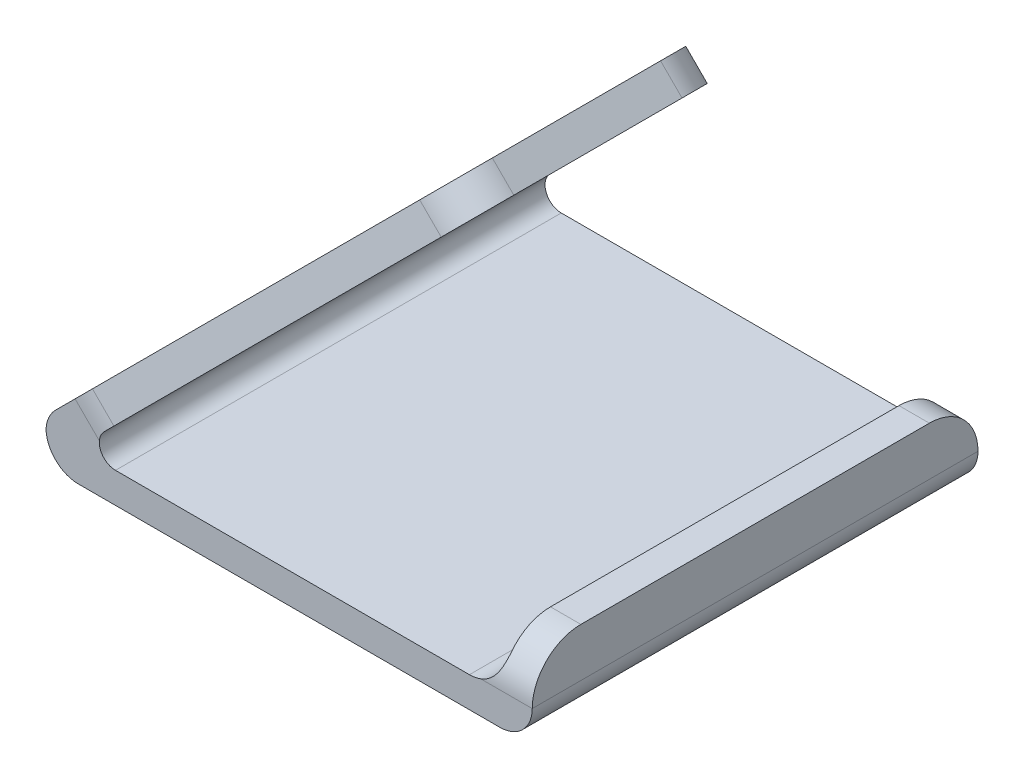
SolidWorks part; units mm, degrees
ref_plane "Front Plane" through (0, 0, 0) normal (0, 0, 1) x (1, 0, 0)
ref_plane "Top Plane" through (0, 0, 0) normal (0, 1, 0) x (1, 0, 0)
ref_plane "Right Plane" through (0, 0, 0) normal (1, 0, 0) x (0, 0, -1)
sketch "Sketch1" plane through (0, 0, 0) normal (0, 0, 1) x (1, 0, 0)
  line L0 (-76.2, 6.7352) -> (-27.9984, 54.9368)
  line L1 (0, 0) -> (-76.2, 0)
  line L2 (0, 0) -> (0, 6.6302)
  line L3 (-4.7625, 4.7625) -> (-71.4375, 4.7625)
  line L4 (-76.2, 0) -> (-76.2, 6.7352)
  line L5 (-27.9984, 54.9368) -> (-24.6308, 51.5692)
  line L6 (-24.6308, 51.5692) -> (-71.4375, 4.7625)
  line L7 (-4.7625, 4.7625) -> (-4.7625, 12.7)
  line L8 (-4.7625, 12.7) -> (0, 12.7)
  line L9 (0, 12.7) -> (0, 6.6302)
  line L10 (-24.6308, 51.5692) -> (-4.7625, 4.7625) construction
  dimension "D1" = 4.7625
  dimension "D2" = 4.7625
  dimension "D3" = 4.7625
  dimension "D4" = 45
  dimension "D5" = 76.2
  dimension "D6" = 4.7625
  dimension "D7" = 23
  dimension "D8" = 12.7
extrude "Boss-Extrude1" add sketch "Sketch1" along normal blind 69.85
fillet "Fillet1" radius 5.08 4 edges at (-76.2, 0, 34.925) (-76.2, 6.7352, 34.925) (0, 0, 34.925) (-4.7625, 4.7625, 34.925)
fillet "Fillet3" radius 2.54 1 edges at (-71.4375, 4.7625, 34.925)
sketch "Sketch2" plane through (-41.4676, 41.4676, 0) normal (-0.7071, 0.7071, 0) x (0, 0, 1)
  line L0 (15.875, 19.0484) -> (0, -41.0142)
  line L1 (69.85, 19.0484) -> (0, 19.0484) construction
  line L2 (69.85, -41.0142) -> (0, -41.0142) construction
  line L3 (0, -41.0142) -> (0, 19.0484)
  line L4 (0, 19.0484) -> (15.875, 19.0484)
  line L5 (69.85, 19.0484) -> (53.975, 19.0484)
  line L6 (53.975, 19.0484) -> (69.85, -41.0142)
  line L8 (69.85, -41.0142) -> (69.85, 19.0484)
  line L9 (15.875, 19.0484) -> (53.975, 19.0484) construction
  point P14 (34.925, 19.0484)
  point P15 (34.925, 19.0484)
  dimension "D1" = 38.1
extrude "Cut-Extrude1" cut sketch "Sketch2" against normal up to next
fillet "Fillet2" radius 7.62 4 edges at (-2.3812, 12.7, 0) (-2.3812, 12.7, 69.85) (-26.3146, 53.253, 53.975) (-26.3146, 53.253, 15.875)
fillet "Fillet4" radius 12.7 2 edges at (-68.7852, 10.7823, 0) (-68.7852, 10.7823, 69.85)
